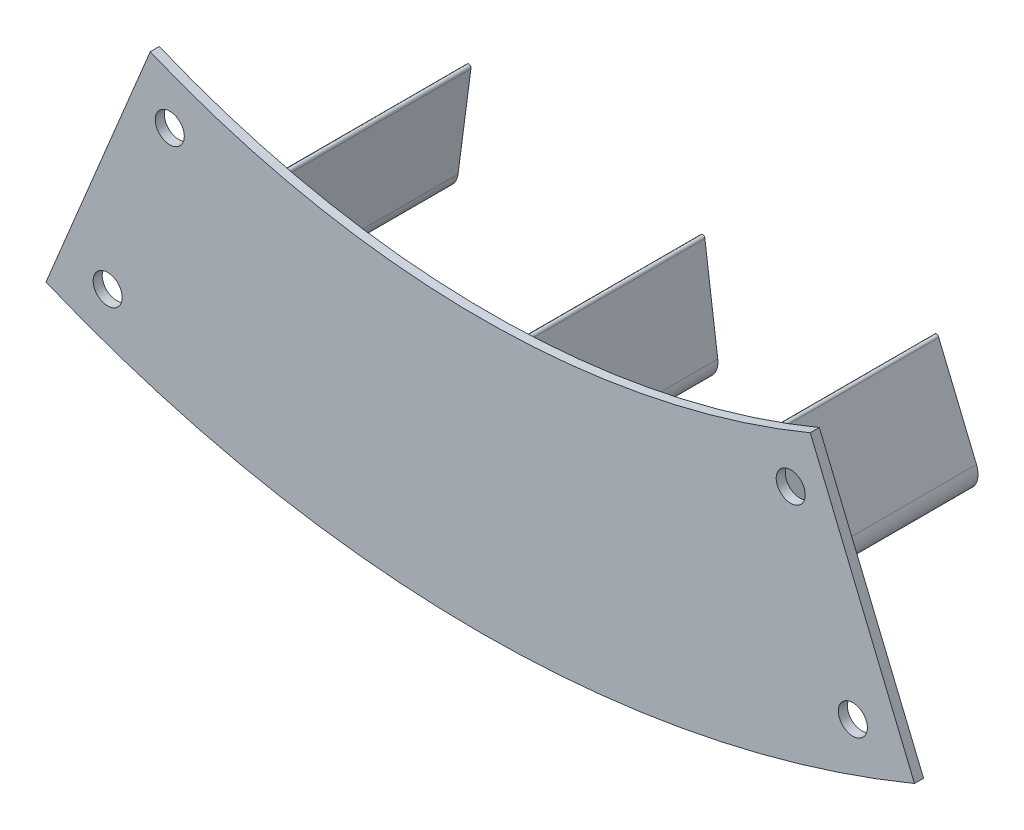
SolidWorks part; units mm, degrees
note: The reader was unsure of these and kept them because the rebuilt part matched: shared geometry of "Sketch1<3>", "Sketch1<4>".
ref_plane "Front Plane" through (0, 0, 0) normal (0, 0, 1) x (1, 0, 0)
ref_plane "Top Plane" through (0, 0, 0) normal (0, 1, 0) x (1, 0, 0)
ref_plane "Right Plane" through (0, 0, 0) normal (1, 0, 0) x (0, 0, -1)
sketch "Sketch1" plane through (0, 0, 0) normal (0, 0, 1) x (1, 0, 0)
  line L2 (23.5925, -98.463) -> (25.4301, -105.7349) construction
  line L3 (-25.4301, -105.7349) -> (-23.5925, -98.463) construction
  line L4 (23.9559, -97.8605) -> (26.0385, -106.1017)
  line L5 (-26.0385, -106.1017) -> (-23.9559, -97.8605)
  line L6 (-47.8354, -115.4849) -> (-36.3549, -87.7686)
  line L9 (47.8354, -115.4849) -> (36.3549, -87.7686)
  arc A2 (-25.4301, -105.7349) -> (25.4301, -105.7349) centre (0, 0) ccw construction
  arc A3 (-23.5925, -98.463) -> (23.5925, -98.463) centre (0, 0) ccw construction
  arc A4 (-26.0385, -106.1017) -> (26.0385, -106.1017) centre (0, 0) ccw
  arc A5 (-23.9559, -97.8605) -> (23.9559, -97.8605) centre (0, 0) ccw
  arc A6 (-36.3549, -87.7686) -> (36.3549, -87.7686) centre (0, 0) ccw
  arc A7 (-47.8354, -115.4849) -> (47.8354, -115.4849) centre (0, 0) ccw
  dimension "D2" = 95
  dimension "D3" = 125
  dimension "D4" = 45
  dimension "D5" = 30
  dimension "D6" = 87.7686
  dimension "D1" = 0.5
extrude "Boss-Extrude1" add sketch "Sketch1" against normal blind 1 from surface at -5 contours L6 A7 L9 A6 L5 A5 L4 A4
extrude "Boss-Extrude2" add sketch "Sketch1<3>" along normal up to surface (5 mm away) from surface separate body contours A5 L5 A4 L4
sketch "Sketch1<3>" plane through (0, 0, 0) normal (0, 0, 1) x (1, 0, 0) same geometry as "Sketch1"
extrude "Boss-Extrude3" add sketch "Sketch1<4>" along normal blind 1 and the other way up to surface (6 mm away) contours A5 L5 A4 L4 other way up to face at (0, -103.4905, -6)
sketch "Sketch1<4>" plane through (0, 0, 0) normal (0, 0, 1) x (1, 0, 0) same geometry as "Sketch1"
sketch "Sketch3" plane through (0, 0, -6) normal (0, 0, -1) x (-1, 0, 0)
  line L0 (-26.7265, -95.8811) -> (-30.8555, -105.8494) construction
  line L1 (-24.7947, -96.3987) -> (-26.203, -107.096) construction
  line L2 (-26.7265, -95.8811) -> (-30.8555, -105.8494) construction
  line L3 (-24.7947, -96.3987) -> (-26.203, -107.096) construction
  line L4 (1, -99.5313) -> (2.4083, -110.2286) construction
  line L5 (-1, -99.5313) -> (-2.4083, -110.2286) construction
  line L6 (1, -99.5313) -> (2.4083, -110.2286) construction
  line L7 (-1, -99.5313) -> (-2.4083, -110.2286) construction
  line L8 (26.7265, -95.8811) -> (30.8555, -105.8494) construction
  line L9 (24.7947, -96.3987) -> (26.203, -107.096) construction
  line L10 (26.7265, -95.8811) -> (30.8555, -105.8494) construction
  line L11 (24.7947, -96.3987) -> (26.203, -107.096) construction
  line L12 (-25.5297, -96.2357) -> (-26.9466, -106.9981)
  line L13 (-26.0085, -96.1074) -> (-30.1626, -106.1364)
  line L14 (0.2478, -99.5641) -> (1.6647, -110.3265)
  line L15 (-0.2478, -99.5641) -> (-1.6647, -110.3265)
  line L16 (26.0085, -96.1074) -> (30.1626, -106.1364)
  line L17 (25.5297, -96.2357) -> (26.9466, -106.9981)
  arc A0 (-28.1773, -109.5328) -> (-26.203, -107.096) centre (-29.1773, -106.7044) ccw construction
  arc A2 (-30.8555, -105.8494) -> (-30.3642, -108.9469) centre (-28.0839, -106.9974) ccw construction
  arc A3 (-24.7947, -96.3987) -> (-26.7265, -95.8811) centre (-25.7606, -96.1399) ccw construction
  arc A4 (-28.1773, -109.5328) -> (-26.203, -107.096) centre (-29.1773, -106.7044) ccw construction
  arc A6 (-30.8555, -105.8494) -> (-30.3642, -108.9469) centre (-28.0839, -106.9974) ccw construction
  arc A7 (-24.7947, -96.3987) -> (-26.7265, -95.8811) centre (-25.7606, -96.1399) ccw construction
  arc A8 (1.132, -113.0934) -> (2.4083, -110.2286) centre (-0.566, -110.6202) ccw construction
  arc A10 (-2.4083, -110.2286) -> (-1.132, -113.0934) centre (0.566, -110.6202) ccw construction
  arc A11 (1, -99.5313) -> (-1, -99.5313) centre (0, -99.5313) ccw construction
  arc A12 (1.132, -113.0934) -> (2.4083, -110.2286) centre (-0.566, -110.6202) ccw construction
  arc A14 (-2.4083, -110.2286) -> (-1.132, -113.0934) centre (0.566, -110.6202) ccw construction
  arc A15 (1, -99.5313) -> (-1, -99.5313) centre (0, -99.5313) ccw construction
  arc A16 (30.3642, -108.9469) -> (30.8555, -105.8494) centre (28.0839, -106.9974) ccw construction
  arc A18 (26.203, -107.096) -> (28.1773, -109.5328) centre (29.1773, -106.7044) ccw construction
  arc A19 (26.7265, -95.8811) -> (24.7947, -96.3987) centre (25.7606, -96.1399) ccw construction
  arc A20 (30.3642, -108.9469) -> (30.8555, -105.8494) centre (28.0839, -106.9974) ccw construction
  arc A21 (28.1773, -109.5328) -> (30.3642, -108.9469) centre (-4.4332, 16.5449) ccw construction
  arc A22 (26.203, -107.096) -> (28.1773, -109.5328) centre (29.1773, -106.7044) ccw construction
  arc A23 (26.7265, -95.8811) -> (24.7947, -96.3987) centre (25.7606, -96.1399) ccw construction
  arc A24 (-28.2286, -108.7446) -> (-26.9466, -106.9981) centre (-29.1773, -106.7044) ccw
  arc A25 (-25.5297, -96.2357) -> (-26.0085, -96.1074) centre (-25.7606, -96.1399) ccw
  arc A26 (-30.1626, -106.1364) -> (-29.9256, -108.2899) centre (-28.0839, -106.9974) ccw
  arc A27 (-29.9256, -108.2899) -> (-28.2286, -108.7446) centre (4.4332, 16.5449) ccw construction
  arc A28 (0.8784, -112.3454) -> (1.6647, -110.3265) centre (-0.566, -110.6202) ccw
  arc A29 (0.2478, -99.5641) -> (-0.2478, -99.5641) centre (0, -99.5313) ccw
  arc A30 (-1.6647, -110.3265) -> (-0.8784, -112.3454) centre (0.566, -110.6202) ccw
  arc A31 (-0.8784, -112.3454) -> (0.8784, -112.3454) centre (0, 17.1285) ccw construction
  arc A32 (29.9256, -108.2899) -> (30.1626, -106.1364) centre (28.0839, -106.9974) ccw
  arc A33 (26.0085, -96.1074) -> (25.5297, -96.2357) centre (25.7606, -96.1399) ccw
  arc A34 (26.9466, -106.9981) -> (28.2286, -108.7446) centre (29.1773, -106.7044) ccw
  arc A35 (28.2286, -108.7446) -> (29.9256, -108.2899) centre (-4.4332, 16.5449) ccw construction
  arc A36 (-0.8784, -112.3454) -> (0.8784, -112.3454) centre (0, -111.2962) ccw
  arc A37 (-29.9256, -108.2899) -> (-28.2286, -108.7446) centre (-28.8056, -107.5039) ccw
  arc A38 (28.2286, -108.7446) -> (29.9256, -108.2899) centre (28.8056, -107.5039) ccw
  arc A39 (-1.132, -113.0934) -> (1.132, -113.0934) centre (0, 17.1285) ccw construction
  arc A40 (-30.3642, -108.9469) -> (-28.1773, -109.5328) centre (4.4332, 16.5449) ccw construction
  dimension "D1" = 0.75
extrude "Boss-Extrude4" add sketch "Sketch3" along normal up to surface (23.5 mm away)
sketch "Sketch4" plane through (0, 0, 1) normal (0, 0, 1) x (1, 0, 0)
  line L2 (-23.9559, -97.8605) -> (-26.0385, -106.1017)
  line L3 (26.0385, -106.1017) -> (23.9559, -97.8605)
  line L4 (-23.9559, -97.8605) -> (-26.0385, -106.1017)
  line L5 (26.0385, -106.1017) -> (23.9559, -97.8605)
  arc A2 (-23.9559, -97.8605) -> (23.9559, -97.8605) centre (0, 0) ccw
  arc A3 (-26.0385, -106.1017) -> (26.0385, -106.1017) centre (0, 0) ccw
  arc A4 (-23.9559, -97.8605) -> (23.9559, -97.8605) centre (0, 0) ccw
  arc A5 (-26.0385, -106.1017) -> (26.0385, -106.1017) centre (0, 0) ccw
  dimension "D1" = 0
extrude "Cut-Extrude1" cut sketch "Sketch4" against normal blind 6
sketch "Sketch5" plane through (0, 0, -5) normal (0, 0, 1) x (1, 0, 0)
  line L0 (0, 0) -> (0, -161.873) construction
  line L1 (0, 0) -> (-58.6865, -161.2399) construction
  circle A0 centre (-34.202, -93.9693) radius 1.6
  circle A1 centre (-41.0424, -112.7631) radius 1.6
  circle A2 centre (41.0424, -112.7631) radius 1.6
  circle A3 centre (34.202, -93.9693) radius 1.6
  arc A4 (-34.202, -93.9693) -> (34.202, -93.9693) centre (0, 0) ccw construction
  arc A5 (-41.0424, -112.7631) -> (41.0424, -112.7631) centre (0, 0) ccw construction
  dimension "D1" = 3.2
  dimension "D2" = 100
  dimension "D4" = 120
  dimension "D3" = 20
extrude "Cut-Extrude2" cut sketch "Sketch5" against normal through all both and the other way through all
